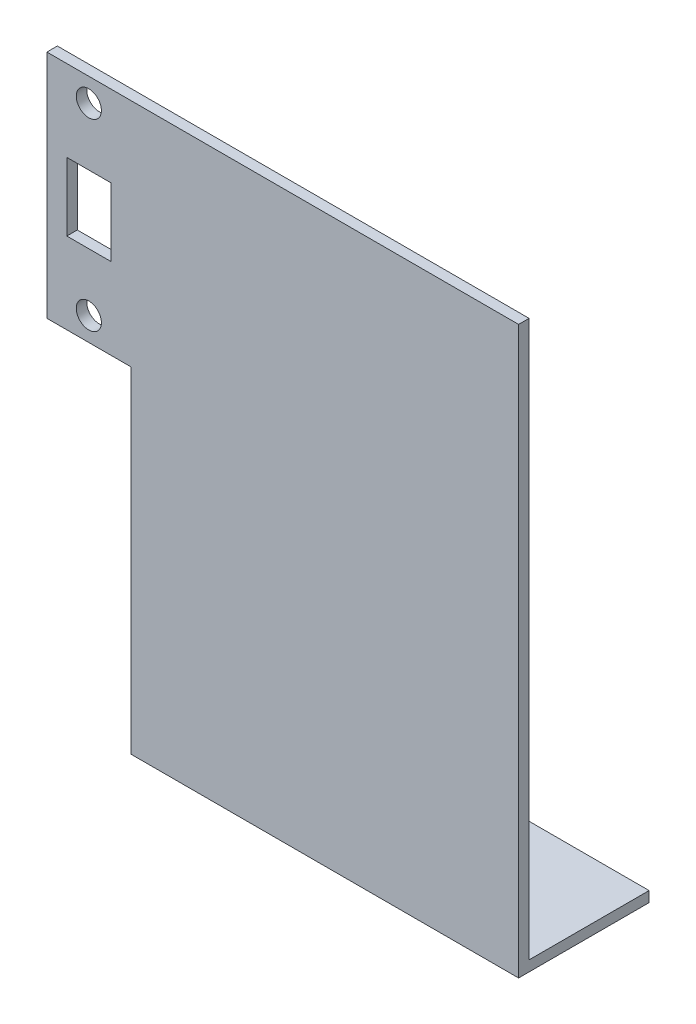
SolidWorks part; units mm, degrees
ref_plane "Front" through (0, 0, 0) normal (0, 0, 1) x (1, 0, 0)
ref_plane "Top" through (0, 0, 0) normal (0, 1, 0) x (1, 0, 0)
ref_plane "Side" through (0, 0, 0) normal (1, 0, 0) x (0, 0, -1)
ref_axis "X_Axis" through (-20.1896, 0, 0) along (1, 0, 0)
ref_axis "Y_Axis" through (0, -14.8261, 0) along (0, 1, 0)
ref_axis "Z_Axis" through (0, 0, -19.842) along (0, 0, 1)
sketch "Sketch1" plane through (0, 0, 0) normal (0, 0, 1) x (1, 0, 0)
  line L4 (18.5, 23.5) -> (18.5, 30.5)
  line L5 (18.5, 30.5) -> (-18.5, 30.5)
  line L7 (-17.5, 29.5) -> (17.5, 29.5) construction
  line L8 (18.5, -23.5) -> (18.5, 23.5)
  line L9 (18.5, 23.5) -> (-18.5, 23.5)
  line L10 (-18.5, 23.5) -> (-18.5, -23.5)
  line L11 (-18.5, -23.5) -> (18.5, -23.5)
  line L12 (18.5, -23.5) -> (18.5, 23.5)
  line L14 (-18.5, 8.5) -> (-18.5, -23.5)
  line L15 (-18.5, -23.5) -> (18.5, -23.5)
  line L16 (-18.5, 30.5) -> (-26.5, 30.5)
  line L17 (-26.5, 30.5) -> (-26.5, 8.5)
  line L18 (-26.5, 8.5) -> (-18.5, 8.5)
  dimension "D2" = 1
  dimension "D3" = 22
  dimension "D4" = 8
  dimension "D1" = 1
extrude "Boss-Extrude1" add sketch "Sketch1" along normal blind 1
sketch "Sketch2" plane through (0, 0, 1) normal (0, 0, 1) x (1, 0, 0)
  line L0 (-22.5, 8.5) -> (-22.5, 30.5) construction
  line L1 (-26.5, 8.5) -> (-18.5, 8.5) construction
  line L2 (18.5, 30.5) -> (-26.5, 30.5) construction
  line L3 (-24.6, 19.5) -> (-20.4, 19.5) construction
  line L4 (-24.6, 22.75) -> (-20.4, 22.75)
  line L5 (-24.6, 22.75) -> (-24.6, 16.25)
  line L6 (-24.6, 16.25) -> (-20.4, 16.25)
  line L7 (-20.4, 22.75) -> (-20.4, 16.25)
  line L8 (-24.6, 22.75) -> (-20.4, 16.25) construction
  line L9 (-24.6, 16.25) -> (-20.4, 22.75) construction
  circle A0 centre (-22.5, 10.735) radius 1.2
  circle A1 centre (-22.5, 28.265) radius 1.2
  point P6 (-22.5, 19.5)
  point P17 (0, 0)
  dimension "D4" = 2.4
  dimension "D1" = 6.5
  dimension "D2" = 4.2
  dimension "D3" = 17.53
extrude "Cut-Extrude1" cut sketch "Sketch2" against normal blind 11
sketch "Sketch3" plane through (0, 0, 0) normal (0, 0, -1) x (-1, 0, 0)
  line L0 (-18.5, -23.5) -> (-18.5, 30.5) construction
  line L1 (18.5, -23.5) -> (-18.5, -23.5)
  line L2 (18.5, -23.5) -> (18.5, -22.5)
  line L3 (18.5, -22.5) -> (-18.5, -22.5)
  line L4 (-18.5, -23.5) -> (-18.5, -22.5)
  line L5 (-15.6833, -22.5) -> (-19.5, -22.5) construction
extrude "Boss-Extrude2" add sketch "Sketch3" along normal up to surface (11.45 mm away)
